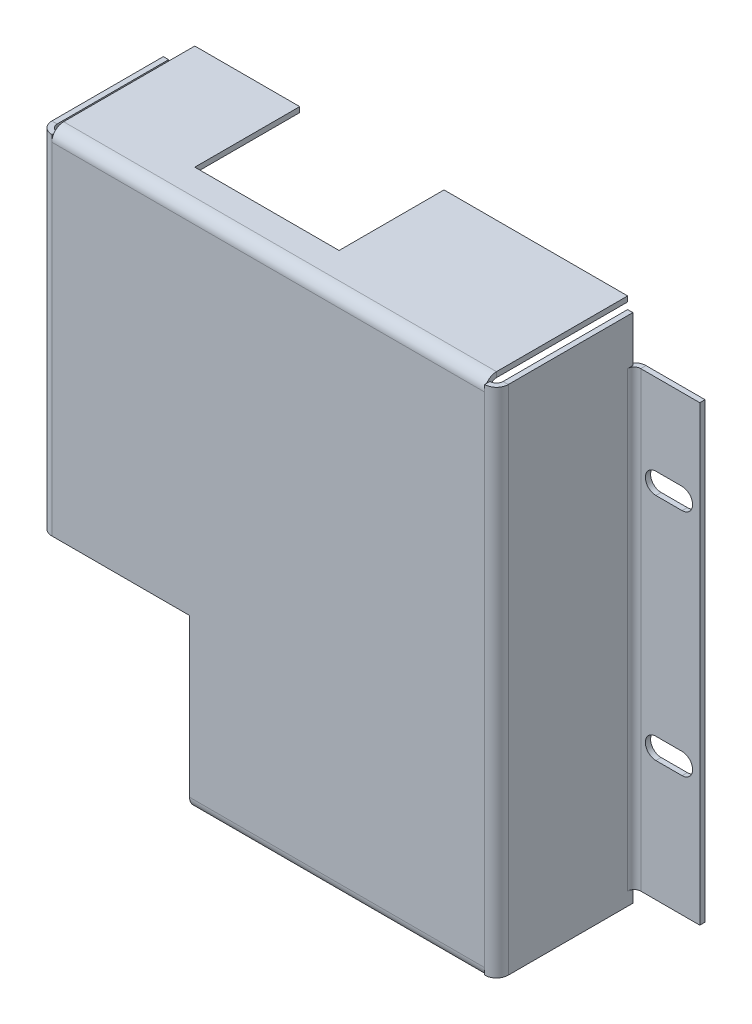
SolidWorks part; units mm, degrees
note: The reader was unsure of these and kept them because the rebuilt part matched: flange length of "Edge-Flange1", "Edge-Flange4", "Edge-Flange6", "Edge-Flange7", "Edge-Flange8".
ref_plane "Front Plane" through (0, 0, 0) normal (0, 0, 1) x (1, 0, 0)
ref_plane "Top Plane" through (0, 0, 0) normal (0, 1, 0) x (1, 0, 0)
ref_plane "Right Plane" through (0, 0, 0) normal (1, 0, 0) x (0, 0, -1)
sketch "Sketch1" plane through (0, 0, 20.5614) normal (0, 0, 1) x (1, 0, 0)
  line L0 (22.1475, -45.9812) -> (-23.8525, -45.9812)
  line L1 (-45.8525, 32.0188) -> (22.1475, 32.0188)
  line L2 (-45.8525, 32.0188) -> (-45.8525, -20.9812)
  line L4 (22.1475, 32.0188) -> (22.1475, -45.9812)
  line L6 (-23.8525, -45.9812) -> (-23.8525, -20.9812)
  line L7 (-23.8525, -20.9812) -> (-45.8525, -20.9812)
  dimension "D4" = 25
  dimension "D1" = 68
  dimension "D2" = 46
  dimension "D3" = 78
sheet metal parameters "Sheet-Metal1" thickness 0.8 parameters "D1"=1
base flange "Base-Flange1" sketch "Sketch1" thickness 0.8 reverse thickness direction yes parameters "D1"=1
ref_plane "Plane1" through (-45.8525, 32.0188, 21.3614) normal (0, -1, 0) x (1, 0, 0)
ref_plane "Plane2" through (-45.8525, 32.0188, 20.5614) normal (0, -1, 0) x (1, 0, 0)
edge flange "Edge-Flange1" sketch "Sketch21" flange angle 90 flange length 18 flange position material outside bend radius 1 thickness 0.8 parameters "D1"=2, "D6"=10
sketch "Sketch21" plane through (-45.8525, 0, 20.5614) normal (-1, 0, 0) x (0, 1, 0)
  line L0 (32.0188, 18) -> (-20.9812, 18)
  line L2 (-20.9812, 18) -> (-20.9812, 0)
  line L4 (32.0188, 18) -> (32.0188, 0)
  line L5 (32.0188, 0) -> (-20.9812, 0) construction
  line L6 (32.0188, 0) -> (-20.9812, 0)
  dimension "D3" = 18
bend "EdgeBend1" bend radius 1 bend angle 90 parameters "D5"=1
edge flange "Edge-Flange4" sketch "Sketch32" flange angle 90 flange length 21 flange position material outside bend radius 1 thickness 0.8 parameters "D1"=2, "D6"=10
sketch "Sketch32" plane through (22.1475, 0, 20.5614) normal (1, 0, 0) x (0, -1, 0)
  line L0 (45.9812, 0) -> (-32.0188, 0) construction
  line L1 (45.9812, 0) -> (-32.0188, 0)
  line L2 (-32.0188, 0) -> (-32.0188, 20)
  line L3 (-32.0188, 20) -> (-25.0188, 20)
  line L4 (45.9812, 20) -> (45.9812, 0)
  line L5 (-25.0188, 20) -> (-25.0188, 21)
  line L6 (-25.0188, 21) -> (43.9812, 21)
  line L7 (43.9812, 21) -> (43.9812, 20)
  line L8 (43.9812, 20) -> (45.9812, 20)
  dimension "D1" = 20
  dimension "D2" = 7
  dimension "D3" = 2
  dimension "D4" = 21
bend "EdgeBend4" bend radius 1 bend angle 90 parameters "D5"=4
edge flange "Edge-Flange6" sketch "Sketch38" flange angle 90 flange length 10 flange position material inside bend radius 1 thickness 0.8 relief none parameters "D6"=10
sketch "Sketch38" plane through (22.9475, 0, -0.4386) normal (0, 0, -1) x (0, 1, 0)
  line L0 (-43.9812, 0) -> (25.0188, 0) construction
  line L1 (-43.9812, 0) -> (25.0188, 0)
  line L2 (-43.9812, 0) -> (-43.9812, 10)
  line L3 (-43.9812, 10) -> (25.0188, 10)
  line L4 (25.0188, 10) -> (25.0188, 0)
  line L5 (11.0188, 7.3) -> (11.0188, 3.3) construction
  line L6 (12.6188, 7.3) -> (12.6188, 3.3)
  line L7 (9.4188, 7.3) -> (9.4188, 3.3)
  line L8 (-23.9812, 7.3) -> (-23.9812, 3.3) construction
  line L9 (-22.3812, 7.3) -> (-22.3812, 3.3)
  line L10 (-25.5812, 7.3) -> (-25.5812, 3.3)
  arc A0 (12.6188, 7.3) -> (9.4188, 7.3) centre (11.0188, 7.3) ccw
  arc A1 (9.4188, 3.3) -> (12.6188, 3.3) centre (11.0188, 3.3) ccw
  arc A2 (-22.3812, 7.3) -> (-25.5812, 7.3) centre (-23.9812, 7.3) ccw
  arc A3 (-25.5812, 3.3) -> (-22.3812, 3.3) centre (-23.9812, 3.3) ccw
  point P7 (11.0188, 5.3)
  point P12 (-23.9812, 5.3)
  dimension "D2" = 1.6
  dimension "D3" = 1.6
  dimension "D6" = 2.7
  dimension "D1" = 10
  dimension "D4" = 4
  dimension "D5" = 4
  dimension "D7" = 2.7
  dimension "D8" = 14
  dimension "D9" = 20
bend "EdgeBend6" bend radius 1 bend angle 90 parameters "D5"=5
edge flange "Edge-Flange7" sketch "Sketch41" flange angle 90 flange length 21 flange position material outside bend radius 1 thickness 0.8 relief none parameters "D1"=2, "D6"=10
sketch "Sketch41" plane through (0, -45.9812, 20.5614) normal (0, -1, 0) x (-1, 0, 0)
  line L0 (23.8525, 0) -> (-21.1475, 0) construction
  line L1 (23.8525, 0) -> (-21.1475, 0)
  line L2 (-21.1475, 0) -> (-21.1475, 21)
  line L3 (-21.1475, 21) -> (23.8525, 21)
  line L4 (23.8525, 21) -> (23.8525, 0)
  dimension "D1" = 21
bend "EdgeBend7" bend radius 1 bend angle 90 parameters "D5"=6
edge flange "Edge-Flange8" sketch "Sketch44" flange angle 90 flange length 21 flange position material outside bend radius 1 thickness 0.8 relief none parameters "D6"=10
sketch "Sketch44" plane through (0, 32.0188, 20.5614) normal (0, 1, 0) x (1, 0, 0)
  line L0 (21.1475, 0) -> (-44.8525, 0) construction
  line L1 (21.1475, 0) -> (-44.8525, 0)
  line L2 (-44.8525, 0) -> (-44.8525, 21)
  line L3 (-44.8525, 21) -> (-28.8525, 21)
  line L4 (21.1475, 21) -> (21.1475, 0)
  line L5 (-28.8525, 21) -> (-28.8525, 5)
  line L6 (-28.8525, 5) -> (-6.8525, 5)
  line L7 (-6.8525, 5) -> (-6.8525, 21)
  line L8 (-6.8525, 21) -> (21.1475, 21)
  dimension "D1" = 21
  dimension "D2" = 16
  dimension "D3" = 28
  dimension "D4" = 5
bend "EdgeBend8" bend radius 1 bend angle 90 parameters "D5"=7
flat pattern "Flat-Pattern1" [suppressed]
sketch "Bend-Lines1" plane through (0, 0, 21.3614) normal (0, 0, 1) x (1, 0, 0)
  line L0 (42.6179, -43.9812) -> (42.6179, 25.0188) construction
  line L1 (22.2376, 32.0188) -> (22.2376, -45.9812) construction
  line L2 (-44.8525, 32.1089) -> (21.1475, 32.1089) construction
  line L3 (21.1475, -46.0714) -> (-23.8525, -46.0714) construction
  line L4 (-45.9427, -20.9812) -> (-45.9427, 32.0188) construction
  line L5 (42.6179, -43.9812) -> (42.6179, 25.0188) construction
  line L6 (22.2376, 32.0188) -> (22.2376, -45.9812) construction
  line L7 (-44.8525, 32.1089) -> (21.1475, 32.1089) construction
  line L8 (21.1475, -46.0714) -> (-23.8525, -46.0714) construction
  line L9 (-45.9427, -20.9812) -> (-45.9427, 32.0188) construction
sketch3d "Bounding-Box1" [suppressed]
  line L0 (98.5605, 74.1803, 0) -> (98.5605, -46.1803, 0) construction
  line L1 (-18.1803, 74.1803, 0) -> (-18.1803, -46.1803, 0) construction
  line L2 (98.5605, 74.1803, 0) -> (-18.1803, 74.1803, 0) construction
  line L3 (98.5605, -46.1803, 0) -> (-18.1803, -46.1803, 0) construction
bend of the flat pattern "Flatten-<EdgeBend1>1"
bend of the flat pattern "Flatten-<EdgeBend4>1"
bend of the flat pattern "Flatten-<EdgeBend6>1"
bend of the flat pattern "Flatten-<EdgeBend7>1"
bend of the flat pattern "Flatten-<EdgeBend8>1"
